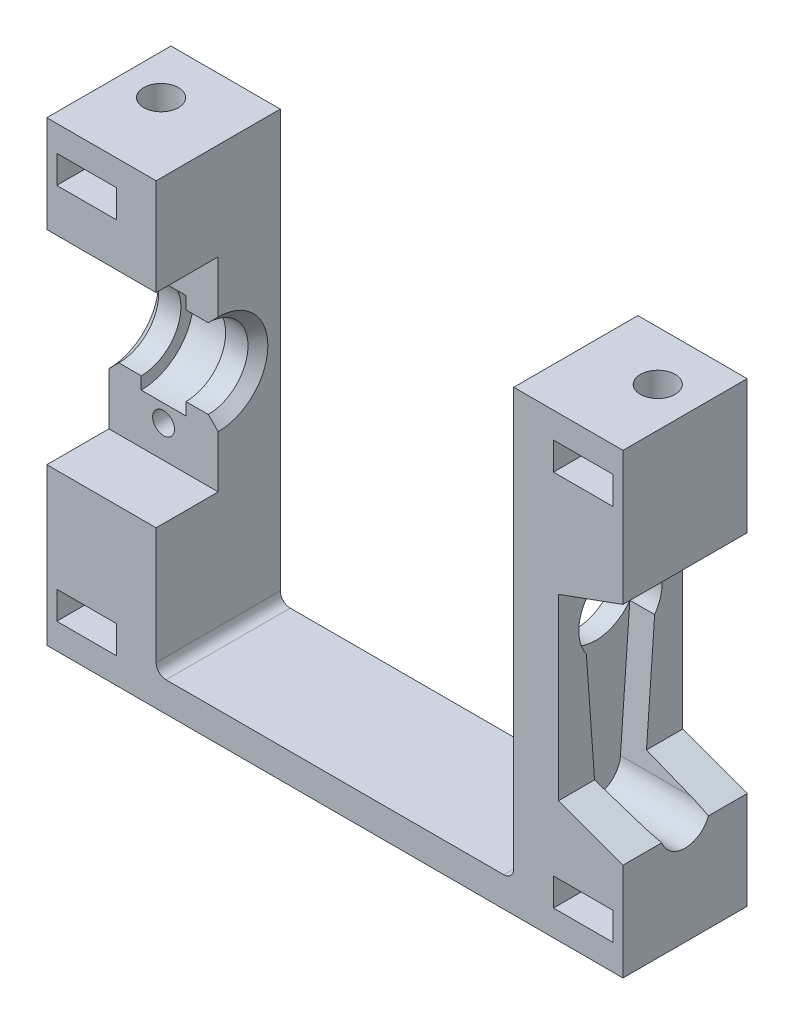
SolidWorks part; units mm, degrees
ref_plane "Спереди" through (0, 0, 0) normal (0, 0, 1) x (1, 0, 0)
ref_plane "Сверху" through (0, 0, 0) normal (0, 1, 0) x (1, 0, 0)
ref_plane "Справа" through (0, 0, 0) normal (1, 0, 0) x (0, 0, -1)
sketch "Эскиз1" plane through (0, 0, 0) normal (0, 0, 1) x (1, 0, 0)
  line L1 (-29, -23) -> (29, -23)
  line L2 (-29, -23) -> (-29, 23)
  line L3 (-29, 23) -> (29, 23)
  line L4 (29, -23) -> (29, 23)
  line L5 (-29, -23) -> (29, 23) construction
  line L6 (-29, 23) -> (29, -23) construction
  point P0 (0, 0)
  dimension "D1" = 58
  dimension "D2" = 46
extrude "тело" add sketch "Эскиз1" along normal blind 12.5
sketch "Эскиз3" plane through (0, 0, 12.5) normal (0, 0, 1) x (1, 0, 0)
  line L1 (-18, -20) -> (18, -20)
  line L2 (-18, -20) -> (-18, 26)
  line L3 (-18, 26) -> (18, 26)
  line L4 (18, -20) -> (18, 26)
  line L5 (-29, -23) -> (29, -23) construction
  point P0 (0, 3)
  point P6 (0, -20)
  point P9 (-18, 3)
  point P10 (0, -23)
  dimension "D1" = 36
  dimension "D2" = 46
  dimension "D3" = 3
extrude "отверстие под серво" cut sketch "Эскиз3" against normal through all
sketch "Эскиз11" plane through (0, -23, 0) normal (0, -1, 0) x (1, 0, 0)
  line L0 (0, 12.5) -> (0, 0) construction
  line L1 (-29, 12.5) -> (29, 12.5) construction
  line L2 (-25, 5) -> (25, 5) construction
  line L3 (-29, 0) -> (29, 0) construction
  circle A0 centre (-25, 5) radius 1.75
  circle A1 centre (25, 5) radius 1.75
  point P8 (0, 5)
  dimension "D1" = 3.5
  dimension "D2" = 50
  dimension "D3" = 5
extrude "Крепежные отверстия сверху" cut sketch "Эскиз11" against normal blind 8
mirror "Крепежные отверстия снизу" about plane through (0, 0, 0) normal (0, 1, 0) of "Крепежные отверстия сверху"
sketch "Эскиз5" plane through (29, 0, 0) normal (1, 0, 0) x (0, 0, -1)
  line L0 (-9.2, 0.7667) -> (-8.2448, -12.4442) construction
  line L1 (-6.25, 3) -> (-6.25, -14.3) construction
  line L2 (-6.25, 6.7) -> (-6.25, -14.3) construction
  line L3 (-9.2, 0.7667) -> (-6.25, 0.7667) construction
  line L4 (-6.25, 0.7667) -> (-6.25, -14.3) construction
  line L5 (-3.3, 0.7667) -> (-4.2552, -12.4442) construction
  line L6 (-9.6884, 0.5881) -> (-8.7435, -12.4803)
  line L7 (-2.8116, 0.5881) -> (-3.7565, -12.4803)
  line L8 (-12.5, -23) -> (0, -23) construction
  line L11 (-12.5, 23) -> (0, 23) construction
  arc A0 (-2.8116, 0.5881) -> (-9.6884, 0.5881) centre (-6.25, 3) ccw
  arc A1 (-8.2448, -12.4442) -> (-4.2552, -12.4442) centre (-6.25, -12.3) ccw construction
  arc A2 (-8.7435, -12.4803) -> (-3.7565, -12.4803) centre (-6.25, -12.3) ccw
  arc A3 (-3.3, 0.7667) -> (-9.2, 0.7667) centre (-6.25, 3) ccw construction
  point P0 (-6.25, -23)
  dimension "D1" = 2.95
  dimension "D2" = 4
  dimension "D4" = 7.4
  dimension "D5" = 0.5
  dimension "D3" = 21
  dimension "D6" = 20
extrude "вырез под качалку" cut sketch "Эскиз5" against normal offset from surface (9 mm away) 2 up to face at (18, 1.5, 6.25)
sketch "Эскиз4" plane through (29, 0, 0) normal (1, 0, 0) x (0, 0, -1)
  line L0 (-6.25, 23) -> (-6.25, -23) construction
  line L1 (-12.5, 23) -> (0, 23) construction
  line L2 (-12.5, -23) -> (0, -23) construction
  line L4 (-12.5, -23) -> (-12.5, 23) construction
  line L5 (-12.5, 0) -> (0, 0) construction
  line L6 (0, -23) -> (0, 23) construction
  circle A0 centre (-6.25, 3) radius 4.2
  arc A1 (-2.8116, 0.5881) -> (-9.6884, 0.5881) centre (-6.25, 3) ccw construction
extrude "вырез под ось вращения" cut sketch "Эскиз4" against normal up to next
sketch "Эскиз6" plane through (-29, 0, 0) normal (-1, 0, 0) x (0, 0, 1)
  circle A0 centre (6.25, 3) radius 4
  dimension "D1" = 8
extrude "вырез под ось подшипника" cut sketch "Эскиз6" against normal up to surface (11 mm away) up to face at (-18, 1.5, 6.25)
sketch "Эскиз7" plane through (-29, 0, 0) normal (-1, 0, 0) x (0, 0, 1)
  line L0 (12.5, 23) -> (12.5, -23) construction
  line L1 (6.25, 13.25) -> (12.5, 13.25)
  line L2 (6.25, 13.25) -> (6.25, -7.25)
  line L3 (6.25, -7.25) -> (12.5, -7.25)
  line L4 (12.5, 13.25) -> (12.5, -7.25)
  point P6 (6.25, 3)
  point P7 (6.25, 3)
  dimension "D1" = 20.5
extrude "вырез под крепление подшипника" cut sketch "Эскиз7" against normal up to surface (11 mm away) up to face at (-18, 3, 10.25)
ref_plane "Плоскость1" through (-23.5, 0, 0) normal (-1, 0, 0) x (0, 0, 1)
sketch "Эскиз8" plane through (-23.5, 0, 0) normal (-1, 0, 0) x (0, 0, 1)
  circle A0 centre (6.25, 3) radius 5.25
  dimension "D1" = 10.5
extrude "вырез под подшипник" cut sketch "Эскиз8" against normal mid plane 4.5
sketch "Эскиз9" plane through (0, 0, 6.25) normal (0, 0, 1) x (1, 0, 0)
  line L1 (-29, 3) -> (-18, 3) construction
  line L3 (-29, 7) -> (-29, -1) construction
  line L4 (-18, -1) -> (-18, 7) construction
  line L5 (-23.5, -4) -> (-23.5, 10) construction
  circle A0 centre (-23.5, 10) radius 1.1
  circle A1 centre (-23.5, -4) radius 1.1
  point P9 (-23.5, 3)
  dimension "D1" = 2.2
  dimension "D2" = 14
extrude "отверстия под саморезы" cut sketch "Эскиз9" against normal offset from surface (5.25 mm away) 1 up to face at (0, 0.75, 0)
sketch "Эскиз10" plane through (0, 0, 12.5) normal (0, 0, 1) x (1, 0, 0)
  line L1 (29, -23) -> (29, 23) construction
  line L2 (18, -20) -> (18, 23) construction
  line L3 (29, -13.1658) -> (29, 9.5658)
  line L4 (22.5, -10.8) -> (22.5, 7.2)
  line L5 (29, 9.5658) -> (22.5, 7.2)
  line L6 (22.5, -10.8) -> (29, -13.1658)
  line L8 (29, 7.2) -> (18, 7.2) construction
  dimension "D1" = 70
  dimension "D2" = 4.5
  dimension "D3" = 18
  dimension "D4" = 70
extrude "вырез чтобы вставлять качалку" cut sketch "Эскиз10" against normal through all
chamfer "Фаска1" distance 1 angle 45 2 edges at (-29, 3, 2.25) (-18, 3, 2.25)
fillet "Скругление1" radius 1 2 edges at (18, -20, 6.25) (-18, -20, 6.25)
sketch "Эскиз12" plane through (0, 0, 0) normal (0, 0, 1) x (1, 0, 0)
  line L0 (-17, -20) -> (17, -20) construction
  line L1 (-10, -20) -> (10, -20)
  line L2 (-10, -20) -> (-10, -21.5)
  line L3 (-10, -21.5) -> (10, -21.5)
  line L4 (10, -20) -> (10, -21.5)
  point P6 (0, -20)
  dimension "D1" = 20
  dimension "D2" = 1.5
extrude "вырез под шлейф" [suppressed] cut sketch "Эскиз12" along normal through all
fillet "Скругление2" [suppressed] radius 0.5
sketch "Эскиз13" [suppressed] plane through (0, 0, 12.5) normal (0, 0, 1) x (1, 0, 0)
  line L1 (-18, 24) -> (18, 24)
  line L2 (-18, 24) -> (-18, 23)
  line L3 (-18, 23) -> (18, 23)
  line L4 (18, 24) -> (18, 23)
  line L5 (29, 23) -> (18, 23) construction
extrude "Удаление нижней перекладины" [suppressed] cut sketch "Эскиз13" against normal up to next
sketch "Эскиз14" plane through (0, 23, 0) normal (0, 1, 0) x (1, 0, 0)
  line L0 (-29, -12.5) -> (-29, -28)
  line L1 (0, 0) -> (0, -28) construction
  line L2 (-29, -12.5) -> (-18, -12.5)
  line L3 (-18, -12.5) -> (-18, -24.5)
  line L4 (-18, -24.5) -> (18, -24.5)
  line L5 (-29, -28) -> (29, -28)
  line L6 (18, -12.5) -> (18, -24.5)
  line L7 (29, -12.5) -> (18, -12.5)
  line L8 (29, -12.5) -> (29, -28)
  point P13 (0, -24.5)
  dimension "D1" = 15.5
  dimension "D2" = 12
extrude "Нижняя скоба жесткости" [suppressed] add sketch "Эскиз14" against normal blind 5
fillet "Скругление3" [suppressed] radius 10
fillet "Скругление4" [suppressed] radius 1.5
sketch "Эскиз15" [suppressed] plane through (0, 0, 0) normal (0, 0, -1) x (-1, 0, 0)
  line L0 (0, 23) -> (0, 0) construction
  line L1 (-18, 23) -> (18, 23) construction
  line L2 (-29, 23) -> (-18, 23) construction
  line L4 (-27.7202, 9.1) -> (-29, 9.5658)
  line L5 (-34, 23) -> (-29, 23)
  line L6 (-29, 9.5658) -> (-29, 23) construction
  line L7 (-29, 9.5658) -> (-22.5, 7.2) construction
  line L8 (-29, 9.5658) -> (-29, 23)
  line L9 (-34, 16.05) -> (-29, 16.05) construction
  line L10 (-34, 9.1) -> (-27.7202, 9.1)
  line L11 (34, 9.1) -> (29, 9.1)
  line L12 (34, 23) -> (29, 23)
  line L13 (29, 23) -> (29, -23) construction
  line L14 (29, 23) -> (29, 9.1)
  arc A0 (-36.5156, 11.2153) -> (-36.5156, 20.8847) centre (-34, 16.05) ccw
  arc A1 (-34, 23) -> (-37.208, 22.2153) centre (-34, 16.05) ccw
  arc A2 (-37.208, 22.2153) -> (-36.5156, 20.8847) centre (-36.8618, 21.55) ccw
  arc A4 (-37.208, 9.8847) -> (-36.5156, 11.2153) centre (-36.8618, 10.55) cw
  arc A5 (-37.208, 9.8847) -> (-34, 9.1) centre (-34, 16.05) ccw
  arc A6 (37.208, 9.8847) -> (34, 9.1) centre (34, 16.05) cw
  arc A7 (37.208, 9.8847) -> (36.5156, 11.2153) centre (36.8618, 10.55) ccw
  arc A8 (34, 23) -> (37.208, 22.2153) centre (34, 16.05) cw
  arc A9 (37.208, 22.2153) -> (36.5156, 20.8847) centre (36.8618, 21.55) cw
  arc A10 (36.5156, 11.2153) -> (36.5156, 20.8847) centre (34, 16.05) cw
  dimension "D1" = 10.9
  dimension "D2" = 1.5
  dimension "D3" = 34
  dimension "D4" = 11
extrude "Крепление фар" [suppressed] add sketch "Эскиз15" against normal blind 12.5
fillet "Скругление5" [suppressed] radius 1
sketch "Эскиз17" plane through (0, 23, 0) normal (0, 1, 0) x (1, 0, 0)
  line L1 (22, -3.2679) -> (22, -6.7321)
  line L2 (22, -6.7321) -> (25, -8.4641)
  line L3 (25, -8.4641) -> (28, -6.7321)
  line L4 (28, -6.7321) -> (28, -3.2679)
  line L5 (28, -3.2679) -> (25, -1.5359)
  line L6 (25, -1.5359) -> (22, -3.2679)
  circle A0 centre (25, -5) radius 3 construction
  dimension "D1" = 6
extrude "Под гайки" cut sketch "Эскиз17" against normal mid plane 2.8 from offset 4 offset against normal yes
sketch "Эскиз18" plane through (29, 0, 12.5) normal (0, 0, 1) x (1, 0, 0)
  line L1 (-1, 20.4) -> (-7, 20.4)
  line L2 (-1, 20.4) -> (-1, 17.6)
  line L3 (-1, 17.6) -> (-7, 17.6)
  line L4 (-7, 20.4) -> (-7, 17.6)
extrude "Для вставки гайки" cut sketch "Эскиз18" against normal up to next
mirror "Зеркальное отражение1" about plane through (0, 0, 0) normal (1, 0, 0) of "Для вставки гайки", "Под гайки"
mirror "Зеркальное отражение2" about plane through (0, 0, 0) normal (0, 1, 0) of "Зеркальное отражение1", "Для вставки гайки", "Под гайки"
sketch "Эскиз19" plane through (0, 0, 12.5) normal (0, 0, 1) x (1, 0, 0)
  line L0 (31.3707, 11.4653) -> (11.652, 11.4653)
  line L1 (11.652, 11.4653) -> (-24.0509, 27.3)
  line L2 (-24.0509, 27.3) -> (-36.2257, 27.3)
  line L3 (-36.2257, 27.3) -> (-36.2257, -26.6278)
  line L4 (-36.2257, -26.6278) -> (31.3707, -25.5821)
  line L5 (31.3707, -25.5821) -> (31.3707, 11.4653)
extrude "Вырез-Вытянуть1" [suppressed] cut sketch "Эскиз19" against normal through all
